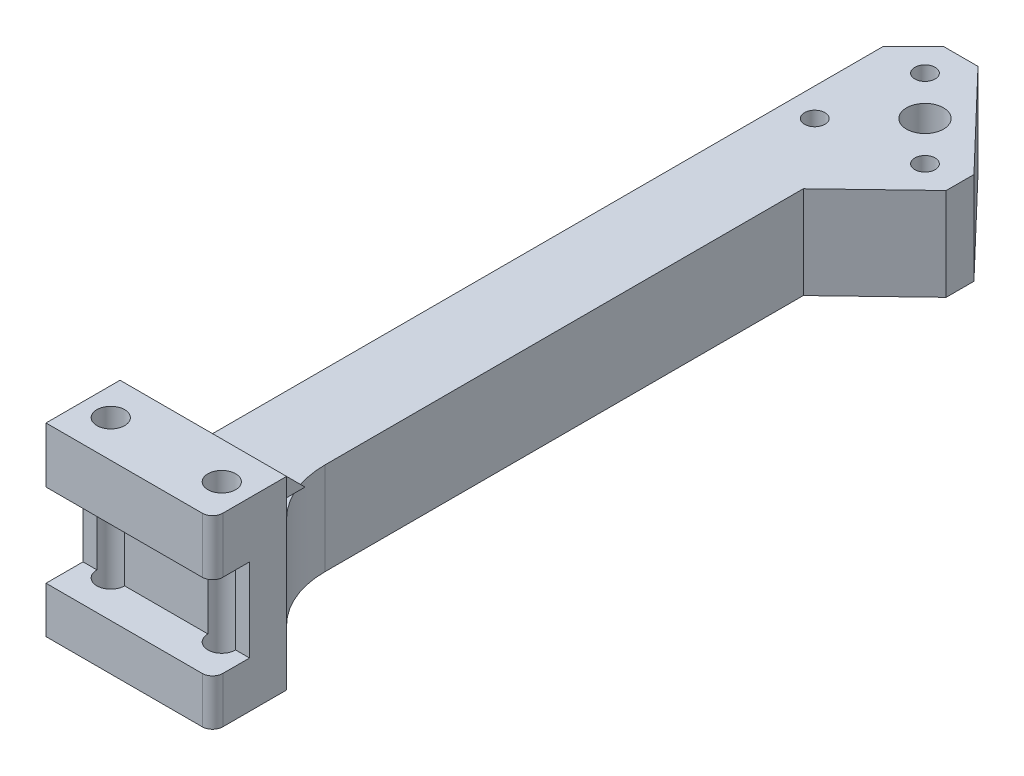
SolidWorks part; units mm, degrees
ref_plane "Front Plane" through (0, 0, 0) normal (0, 0, 1) x (1, 0, 0)
ref_plane "Top Plane" through (0, 0, 0) normal (0, 1, 0) x (1, 0, 0)
ref_plane "Right Plane" through (0, 0, 0) normal (1, 0, 0) x (0, 0, -1)
sketch "Sketch1" plane through (0, 0, 0) normal (0, 1, 0) x (1, 0, 0)
  line L0 (0, 90.435) -> (0, 0)
  line L1 (0, 0) -> (16.8886, 0)
  line L2 (18, 1.1114) -> (18, 8)
  line L3 (18, 8) -> (11.9289, 14.0711)
  line L4 (9, 21.1421) -> (9, 72.8487)
  line L5 (9, 72.8487) -> (9, 86) construction
  line L6 (3, 4) -> (15, 4) construction
  line L7 (0, 90.435) -> (3.3076, 93.7426)
  line L8 (3.3076, 93.7426) -> (6.9872, 93.7426)
  line L9 (6.9872, 93.7426) -> (16.8886, 83.4027)
  line L10 (16.8886, 83.4027) -> (16.8886, 80.4027)
  line L11 (16.8886, 80.4027) -> (9, 72.8487)
  line L12 (9, 86) -> (13.2426, 81.7574) construction
  line L13 (3.0415, 80.0415) -> (9, 86) construction
  line L14 (4.7574, 90.2426) -> (9, 86) construction
  circle A0 centre (9, 86) radius 6 construction
  circle A1 centre (9, 86) radius 8 construction
  circle A2 centre (3, 4) radius 1.5
  circle A3 centre (15, 4) radius 1.5
  arc A4 (16.8886, 0) -> (18, 1.1114) centre (16.8886, 1.1114) ccw
  circle A5 centre (13.2426, 81.7574) radius 1.1
  circle A6 centre (3.0415, 80.0415) radius 1.1
  circle A7 centre (4.7574, 90.2426) radius 1.1
  circle A8 centre (9, 86) radius 2
  arc A9 (11.9289, 14.0711) -> (9, 21.1421) centre (19, 21.1421) cw
  point P16 (18, 0)
  point P28 (3.8101, 93.7426)
  point P29 (0, 0)
  point P30 (0, 0)
  point P31 (0, 0)
  point P32 (9.4233, 93.7426)
  point P33 (8.7215, 93.7426)
  point P34 (6.9872, 93.7426)
  point P35 (6.9872, 93.7426)
  point P36 (0, 0)
  point P37 (0, 0)
  point P38 (0, 0)
  point P39 (0, 0)
  point P40 (0, 0)
  point P41 (6.9872, 93.7426)
  point P42 (0, 0)
  point P43 (6.9872, 93.7426)
  point P44 (6.9872, 93.7426)
  point P45 (15, 81.7574)
  point P46 (15, 81.7574)
  point P47 (15, 83.3009)
  point P48 (15, 84.4013)
  point P49 (15, 78.5961)
  point P50 (15, 78.5961)
  point P51 (15, 85.3506)
  point P52 (15, 78.5961)
  point P53 (15, 78.5961)
  point P54 (9, 72.8672)
  point P55 (15, 85.3506)
  point P56 (0, 0)
  point P57 (14.9652, 85.3544)
  point P58 (6.9872, 93.7426)
  point P59 (0, 0)
  point P60 (6.9872, 93.7426)
  point P61 (0, 0)
  point P62 (15, 82.3506)
  point P63 (9, 76.6217)
  point P64 (9, 76.6217)
  point P65 (0, 0)
  point P66 (0, 92.3236)
  point P67 (0, 0)
  dimension "D7" = 9
  dimension "D8" = 3
  dimension "D10" = 12
  dimension "D11" = 16
  dimension "D16" = 4
  dimension "D22" = 2.2
  dimension "D23" = 10
  dimension "D2" = 8
  dimension "D3" = 12
  dimension "D4" = 4
  dimension "D5" = 3
  dimension "D6" = 45
  dimension "D9" = 82
  dimension "D12" = 45
  dimension "D13" = 90
  dimension "D14" = 90
  dimension "D15" = 3.5
  dimension "D17" = 3
  dimension "D18" = 3.5
  dimension "D19" = 45
  dimension "D20" = 3.5
  dimension "D21" = 4
  dimension "D24" = 18
extrude "Boss-Extrude1" add sketch "Sketch1" along normal blind 10
sketch "Sketch4" plane through (0, 10, 0) normal (0, 1, 0) x (1, 0, 0)
  line L0 (18, 8) -> (0, 8)
  line L1 (0, 90.435) -> (0, 0) construction
  line L2 (0, 8) -> (0, 0)
  line L3 (0, 0) -> (16.8886, 0)
  line L4 (18, 8) -> (18, 1.1114)
  line L15 (3.3076, 93.7426) -> (0, 90.435)
  line L16 (0, 90.435) -> (0, 0)
  line L17 (0, 0) -> (16.8886, 0)
  line L18 (18, 1.1114) -> (18, 8)
  line L19 (18, 8) -> (11.9289, 14.0711)
  line L20 (9, 21.1421) -> (9, 72.8487)
  line L21 (9, 72.8487) -> (16.8886, 80.4027)
  line L22 (16.8886, 80.4027) -> (16.8886, 83.4027)
  line L23 (16.8886, 83.4027) -> (6.9872, 93.7426)
  line L24 (6.9872, 93.7426) -> (3.3076, 93.7426)
  line L25 (3.3076, 93.7426) -> (0, 90.435)
  line L26 (0, 90.435) -> (0, 0)
  line L27 (0, 0) -> (16.8886, 0)
  line L28 (18, 1.1114) -> (18, 8)
  line L29 (18, 8) -> (11.9289, 14.0711)
  line L30 (9, 21.1421) -> (9, 72.8487)
  line L31 (9, 72.8487) -> (16.8886, 80.4027)
  line L32 (16.8886, 80.4027) -> (16.8886, 83.4027)
  line L33 (16.8886, 83.4027) -> (6.9872, 93.7426)
  line L34 (6.9872, 93.7426) -> (3.3076, 93.7426)
  arc A5 (16.8886, 0) -> (18, 1.1114) centre (16.8886, 1.1114) ccw
  arc A6 (9, 21.1421) -> (11.9289, 14.0711) centre (19, 21.1421) ccw
  arc A8 (9, 21.1421) -> (11.9289, 14.0711) centre (19, 21.1421) ccw
  line M2 (0, 90.435) -> (0, 0)
  line M3 (0, 0) -> (16.8886, 0)
  arc M4 (16.8886, 0) -> (18, 1.1114) centre (16.8886, 1.1114) ccw
  line M5 (18, 1.1114) -> (18, 8)
  circle M13 centre (3, 4) radius 1.5
  circle M14 centre (15, 4) radius 1.5
  dimension "D1" = 0
extrude "Boss-Extrude2" add sketch "Sketch4" along normal blind 10 contours L0 M5 M2 M3 M4 M14 M13 region at (8.9821, 10, -4.0077)
sketch "Sketch5" plane through (0, 0, 0) normal (-1, 0, 0) x (0, 0, 1)
  line L0 (0, 20) -> (0, 0) construction
  line L1 (0, 14) -> (-4, 14)
  line L2 (0, 14) -> (0, 5)
  line L3 (0, 5) -> (-4, 5)
  line L4 (-4, 14) -> (-4, 5)
  line L5 (-8, 20) -> (0, 20) construction
  line L6 (-90.435, 0) -> (0, 0) construction
  dimension "D1" = 6
  dimension "D2" = 4
  dimension "D3" = 5
extrude "Cut-Extrude1" cut sketch "Sketch5" against normal through all
sketch "Sketch6" plane through (0, 0, 0) normal (-1, 0, 0) x (0, 0, 1)
  line L0 (-8, 20) -> (-18, 10)
  line L1 (-90.435, 10) -> (-8, 10) construction
  line L14 (0, 0) -> (0, 5)
  line L15 (0, 5) -> (-4, 5)
  line L16 (-4, 5) -> (-4, 14)
  line L17 (-4, 14) -> (0, 14)
  line L18 (0, 14) -> (0, 20)
  line L19 (0, 20) -> (-8, 20)
  line L20 (-8, 20) -> (-8, 10)
  line L21 (-8, 10) -> (-90.435, 10)
  line L22 (-90.435, 10) -> (-90.435, 0)
  line L23 (-90.435, 0) -> (0, 0)
  line L30 (-8, 20) -> (-8, 10)
  line L31 (-8, 10) -> (-18, 10)
  dimension "D1" = 45
  dimension "D2" = 0
extrude "Boss-Extrude3" add sketch "Sketch6" against normal blind 10
